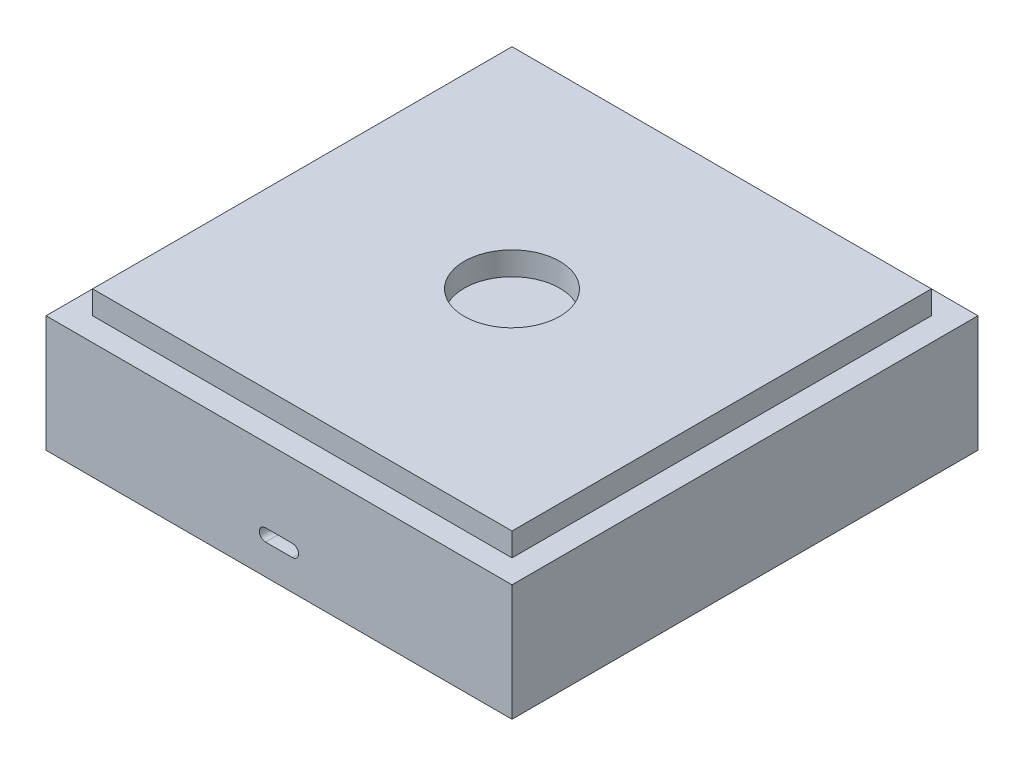
SolidWorks part; units mm, degrees
ref_plane "Front Plane" through (0, 0, 0) normal (0, 0, 1) x (1, 0, 0)
ref_plane "Top Plane" through (0, 0, 0) normal (0, 1, 0) x (1, 0, 0)
ref_plane "Right Plane" through (0, 0, 0) normal (1, 0, 0) x (0, 0, -1)
sketch "Sketch1" plane through (0, 0, 0) normal (0, 1, 0) x (1, 0, 0)
  line L0 (0, 0) -> (5, 0)
  line L1 (0, 0) -> (100, 0)
  line L2 (0, 0) -> (0, -100)
  line L3 (0, -100) -> (100, -100)
  line L4 (100, 0) -> (100, -100)
  line L5 (5, 0) -> (5, -100)
  line L6 (0, 0) -> (0, -5)
  line L7 (0, -5) -> (100, -5)
  line L8 (0, -100) -> (0, -95)
  line L9 (0, -95) -> (100, -95)
  line L10 (100, -100) -> (95, -100)
  line L11 (95, -100) -> (95, 0)
extrude "Boss-Extrude2" add sketch "Sketch1" along normal blind 25 contours L2 L9 L5 L7 | L3 L11 L9 L5 | L9 L2 L3 L5 | L11 L3 L4 L9 | L11 L9 L4 L7 | L7 L11 L1 L5 | L11 L7 L4 L1 | L2 L7 L5 L0 region at (2.5, 0, 2.5) region at (50, 0, 2.5) region at (2.5, 0, 50) region at (97.5, 0, 2.5) region at (2.5, 0, 97.5) region at (97.5, 0, 50) region at (50, 0, 97.5) region at (97.5, 0, 97.5)
extrude "Boss-Extrude3" add sketch "Sketch1<3>" along normal blind 5 contours L9 L11 L7 L5 region at (50, 0, 50)
sketch "Sketch1<3>" plane through (0, 0, 0) normal (0, 1, 0) x (1, 0, 0) same geometry as "Sketch1"
sketch "Sketch3" plane through (0, 25, 0) normal (0, 1, 0) x (1, 0, 0)
  line L5 (5, -5) -> (95, -5)
  line L6 (5, -5) -> (5, -95)
  line L7 (5, -95) -> (95, -95)
  line L8 (95, -5) -> (95, -95)
  circle A0 centre (50, -50) radius 10.25
extrude "Boss-Extrude7" add sketch "Sketch3" along normal blind 5 separate body
sketch "Sketch5" plane through (0, 0, 100) normal (0, 0, 1) x (1, 0, 0)
  line L0 (50, 0) -> (50, 6.5)
  line L1 (0, 0) -> (100, 0) construction
  line L2 (47.11, 6.5) -> (52.89, 6.5)
  line L3 (52.89, 6.5) -> (52.89, 9.14)
  line L4 (47.11, 6.5) -> (47.11, 9.14)
  line L5 (47.11, 9.14) -> (52.89, 9.14)
  arc A1 (52.89, 6.5) -> (52.89, 9.14) centre (52.89, 7.82) ccw
  arc A2 (47.11, 6.5) -> (47.11, 9.14) centre (47.11, 7.82) cw
  point P7 (50, 6.5)
extrude "Cut-Extrude1" cut sketch "Sketch5" against normal blind 10 contours A2 L4 | L5 L4 L2 L3 | L3 A1 region at (50, 7.82, 100) region at (46.5498, 7.82, 100) region at (53.4502, 7.82, 100)
